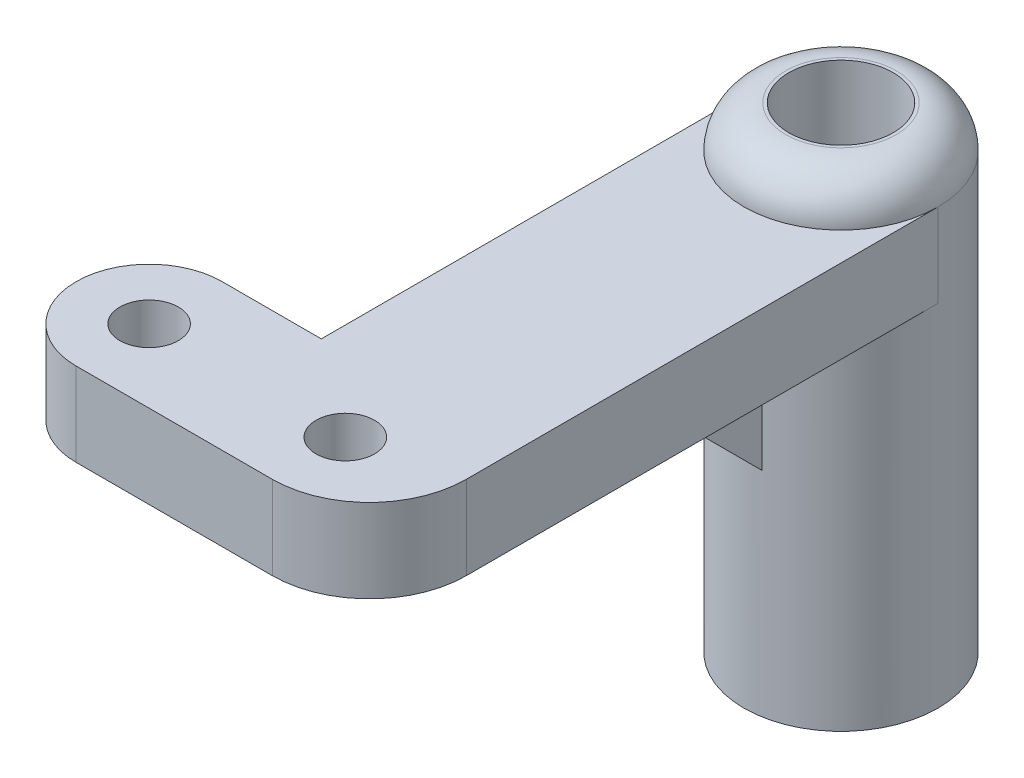
SolidWorks part; units mm, degrees
ref_plane "Front Plane" through (0, 0, 0) normal (0, 0, 1) x (1, 0, 0)
ref_plane "Top Plane" through (0, 0, 0) normal (0, 1, 0) x (1, 0, 0)
ref_plane "Right Plane" through (0, 0, 0) normal (1, 0, 0) x (0, 0, -1)
sketch "Sketch2" plane through (0, 0, 0) normal (0, 1, 0) x (1, 0, 0)
  line L0 (0, 0) -> (0, 22.6) construction
  line L1 (-4.65, 0) -> (-4.65, 22.6)
  line L2 (4.65, 0) -> (4.65, 22.6)
  line L3 (0, -1.15) -> (-9.4, -1.15) construction
  line L4 (0, -4.65) -> (-9.4, -4.65)
  line L5 (0, 2.35) -> (-9.4, 2.35)
  arc A0 (-4.65, 0) -> (4.65, 0) centre (0, 0) ccw
  arc A1 (4.65, 22.6) -> (-4.65, 22.6) centre (0, 22.6) ccw
  arc A2 (0, -4.65) -> (0, 2.35) centre (0, -1.15) ccw
  arc A3 (-9.4, 2.35) -> (-9.4, -4.65) centre (-9.4, -1.15) ccw
  circle A4 centre (-9.4, -1.15) radius 1.4
  circle A5 centre (0, -1.15) radius 1.4
  circle A6 centre (0, 22.6) radius 2.5
  point P3 (0, 11.3)
  point P8 (0, 27.25)
  point P9 (0, -4.65)
  point P12 (-4.7, -1.15)
  point P17 (-12.9, -1.15)
  dimension "D5" = 2.8
  dimension "D6" = 5
  dimension "D1" = 9.3
  dimension "D2" = 31.9
  dimension "D3" = 9.4
  dimension "D4" = 7
extrude "Boss-Extrude1" add sketch "Sketch2" along normal blind 4 contours L5 A3 L4 A0 L1 A4 | A0 A2 L5 L1 A5 | A2 A0 L2 A1 L1 L5 region at (-7.8846, 0, 1.3741) region at (-4.5426, 0, -1.175) region at (0.1436, 0, -12.974)
sketch "Sketch3" plane through (0, 0, 0) normal (0, -1, 0) x (1, 0, 0)
  circle A0 centre (0, -22.6) radius 4.65
  circle A1 centre (0, -22.6) radius 2.5 construction
  circle A2 centre (0, -22.6) radius 2.5
extrude "Boss-Extrude2" add sketch "Sketch3" along normal offset from surface (16.8 mm away) 20.8 up to face at (-3.0481, 4, -6.3267)
sketch "Sketch5" plane through (0, 4, 0) normal (0, 1, 0) x (1, 0, 0)
  circle A1 centre (0, 22.6) radius 2.5
  circle A2 centre (0, 22.6) radius 2.5
  circle A3 centre (0, 22.6) radius 4.65
  circle A4 centre (0, 22.6) radius 4.65
  dimension "D1" = 0
  dimension "D2" = 0
extrude "Boss-Extrude3" add sketch "Sketch5" along normal offset from surface (2 mm away) 22.8 up to face at (0, -16.8, -20.1)
fillet "Fillet1" radius 2 1 edges at (0, 6, -17.95)
sketch "Sketch6" plane through (0, 0, 0) normal (1, 0, 0) x (0, 0, -1)
  line L0 (11.45, 0) -> (17.95, -6.5)
  line L1 (17.95, 0) -> (17.95, -16.8) construction
  line L2 (2.35, 0) -> (22.6, 0) construction
  dimension "D1" = 6.5
  dimension "D2" = 45
rib "Rib1" sketch "Sketch6" sketch "Sketch6" thickness 1.6 extrusion direction parallel to sketch draft on no parameters "D1"=1.6
